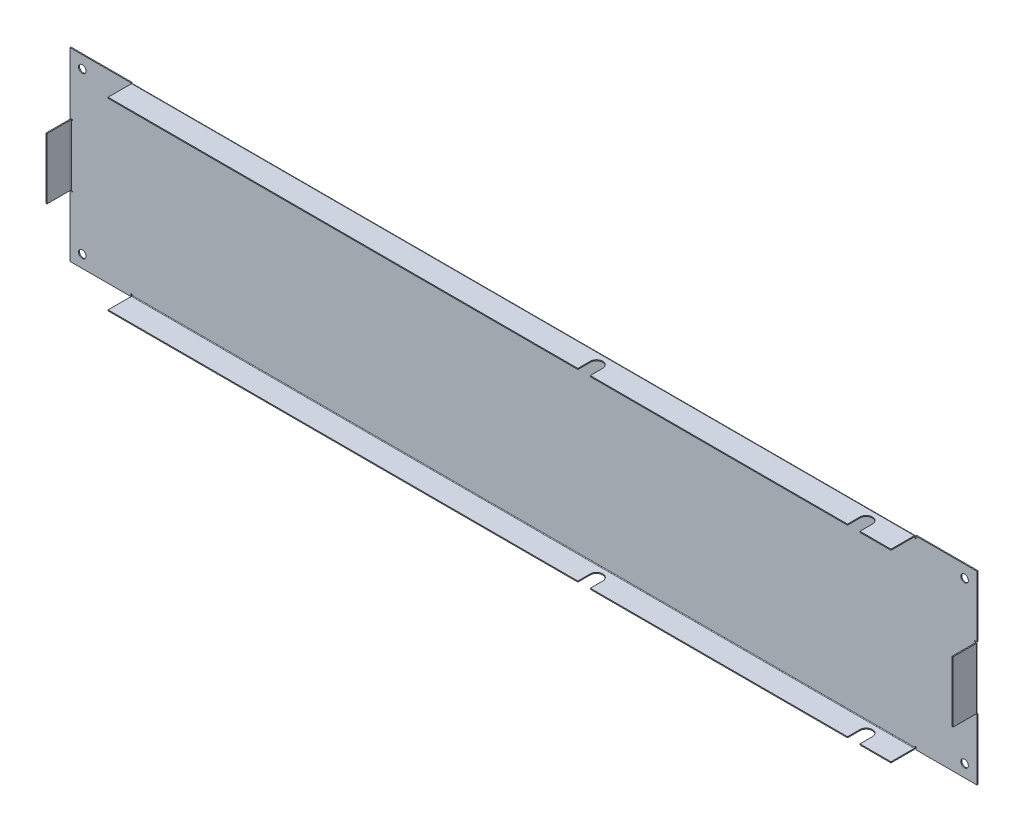
SolidWorks part; units mm, degrees
note: The reader was unsure of these and kept them because the rebuilt part matched: flange length of "边线-法兰1", "边线-法兰2", "边线-法兰3".
ref_plane "前视基准面" through (0, 0, 0) normal (0, 0, 1) x (1, 0, 0)
ref_plane "上视基准面" through (0, 0, 0) normal (0, 1, 0) x (1, 0, 0)
ref_plane "右视基准面" through (0, 0, 0) normal (1, 0, 0) x (0, 0, -1)
sketch "草图1" plane through (0, 0, 0) normal (0, 0, 1) x (1, 0, 0)
  line L1 (-365, 74.5) -> (365, 74.5)
  line L2 (-365, 74.5) -> (-365, -74.5)
  line L3 (-365, -74.5) -> (365, -74.5)
  line L4 (365, 74.5) -> (365, -74.5)
  line L5 (-365, 74.5) -> (365, -74.5) construction
  line L6 (-365, -74.5) -> (365, 74.5) construction
  circle A0 centre (-355, 64.5) radius 3
  circle A1 centre (-355, -64.5) radius 3
  circle A2 centre (355, 64.5) radius 3
  circle A3 centre (355, -64.5) radius 3
  point P0 (0, 0)
  dimension "D11" = 6
  dimension "D1" = 730
  dimension "D2" = 149
  dimension "D3" = 10
  dimension "D4" = 10
  dimension "D5" = 10
  dimension "D6" = 10
  dimension "D7" = 10
  dimension "D8" = 10
  dimension "D9" = 10
  dimension "D10" = 10
base flange "基体-法兰1" sketch "草图1" thickness 0.8 reverse thickness direction no parameters "D1"=0.5
edge flange "边线-法兰1" sketch "草图8" flange angle 90 flange length 20 flange position material inside bend radius 0.5 thickness 0.8 relief rectangular parameters "D6"=10
sketch "草图8" plane through (-365, 0, 0) normal (-1, 0, 0) x (0, -1, 0)
  line L2 (-24.5, 0) -> (-24.5, 19.2)
  line L3 (-24.5, 19.2) -> (24.5, 19.2)
  line L4 (24.5, 19.2) -> (24.5, 0)
  line L5 (-74.5, 0) -> (74.5, 0) construction
  line L6 (-24.5, 0) -> (24.5, 0)
  line L7 (-74.5, -0.8) -> (-74.5, 0) construction
  line L8 (74.5, -0.8) -> (74.5, 0) construction
  line L9 (-74.5, -0.8) -> (74.5, -0.8) construction
  dimension "D1" = 50
  dimension "D2" = 50
  dimension "D3" = 20
bend "边线折弯1" bend radius 0.5 bend angle 90 parameters "D5"=1
edge flange "边线-法兰2" sketch "草图11" flange angle 90 flange length 20 flange position material inside bend radius 0.5 thickness 0.8 relief rectangular parameters "D6"=10
sketch "草图11" plane through (365, 0, 0) normal (1, 0, 0) x (0, 1, 0)
  line L0 (-74.5, 0) -> (74.5, 0) construction
  line L1 (-24.5, 0) -> (24.5, 0)
  line L2 (-24.5, 0) -> (-24.5, 19.2)
  line L3 (-24.5, 19.2) -> (24.5, 19.2)
  line L4 (24.5, 19.2) -> (24.5, 0)
  line L5 (74.5, -0.8) -> (74.5, 0) construction
  line L6 (-74.5, -0.8) -> (74.5, -0.8) construction
  line L7 (-74.5, -0.8) -> (-74.5, 0) construction
  dimension "D1" = 50
  dimension "D2" = 20
  dimension "D3" = 50
bend "边线折弯2" bend radius 0.5 bend angle 90 parameters "D5"=2
edge flange "边线-法兰3" sketch "草图14" flange angle 90 flange length 20 flange position material inside bend radius 0.5 thickness 0.8 relief rectangular parameters "D6"=10
sketch "草图14" plane through (0, 74.5, 0) normal (0, 1, 0) x (-1, 0, 0)
  line L2 (-315, 0) -> (-315, 19.2)
  line L3 (-315, 19.2) -> (-290, 19.2)
  line L4 (315, 19.2) -> (315, 0)
  line L5 (-365, 0) -> (365, 0) construction
  line L6 (-315, 0) -> (315, 0)
  line L7 (-365, -0.8) -> (-365, 0) construction
  line L8 (365, -0.8) -> (365, 0) construction
  line L9 (-290, 9.2) -> (-290, 19.2)
  line L10 (-280, 9.2) -> (-280, 19.2)
  line L11 (-73, 9.2) -> (-73, 19.2)
  line L12 (-63, 9.2) -> (-63, 19.2)
  line L13 (-63, 19.2) -> (315, 19.2)
  line L14 (-280, 19.2) -> (-73, 19.2)
  line L15 (-365, -0.8) -> (365, -0.8) construction
  arc A0 (-290, 9.2) -> (-280, 9.2) centre (-285, 9.2) ccw
  arc A1 (-73, 9.2) -> (-63, 9.2) centre (-68, 9.2) ccw
  dimension "D3" = 10
  dimension "D4" = 10
  dimension "D1" = 50
  dimension "D2" = 50
  dimension "D5" = 20
  dimension "D6" = 10
  dimension "D7" = 10
  dimension "D8" = 30
  dimension "D9" = 217
bend "边线折弯3" bend radius 0.5 bend angle 90 parameters "D5"=3
mirror "镜向1" about plane through (0, 0, 0) normal (0, 1, 0) of "边线-法兰3"
bend "镜向折弯1" bend radius 0.5 bend angle 90 parameters "D5"=4
sketch "折弯-线1" plane through (0, 0, 0) normal (0, 1, 0) x (1, 0, 0)
sketch "边界框1" plane through (0, 0, 0) normal (0, 1, 0) x (1, 0, 0)
sheet metal parameters "钣金1" thickness 0.8 parameters "D1"=0.5
flat pattern "平板型式1" [suppressed]
sketch "折弯-线2" plane through (0, 0, 0) normal (0, 1, 0) x (1, 0, 0)
sketch "边界框2" [suppressed] plane through (0, 0, 0) normal (0, 1, 0) x (1, 0, 0)
sheet metal parameters "钣金2" thickness 0.8 parameters "D1"=0.5
flat pattern "平板型式1" [suppressed]
sketch "折弯-线2" plane through (0, 0, 0) normal (0, 1, 0) x (1, 0, 0)
sketch "边界框2" [suppressed] plane through (0, 0, 0) normal (0, 1, 0) x (1, 0, 0)
bend of the flat pattern "展开-<边线折弯1>1"
sheet metal parameters "钣金3" thickness 0.8 parameters "D1"=0.5
flat pattern "平板型式1" [suppressed]
sketch "折弯-线2" plane through (0, 0, 0) normal (0, 1, 0) x (1, 0, 0)
sketch "边界框2" [suppressed] plane through (0, 0, 0) normal (0, 1, 0) x (1, 0, 0)
bend of the flat pattern "展开-<边线折弯1>1"
bend of the flat pattern "展开-<边线折弯2>1"
sheet metal parameters "钣金4" thickness 0.8 parameters "D1"=0.5
flat pattern "平板型式1" [suppressed]
sketch "折弯-线2" plane through (0, 0, 0) normal (0, 1, 0) x (1, 0, 0)
sketch "边界框2" [suppressed] plane through (0, 0, 0) normal (0, 1, 0) x (1, 0, 0)
bend of the flat pattern "展开-<边线折弯1>1"
bend of the flat pattern "展开-<边线折弯2>1"
bend of the flat pattern "展开-<边线折弯3>1"
sheet metal parameters "钣金5" thickness 0.8 parameters "D1"=0.5
flat pattern "平板型式1" [suppressed]
sketch "折弯-线2" plane through (0, 0, 0) normal (0, 1, 0) x (1, 0, 0)
sketch "边界框2" [suppressed] plane through (0, 0, 0) normal (0, 1, 0) x (1, 0, 0)
bend of the flat pattern "展开-<边线折弯1>1"
bend of the flat pattern "展开-<边线折弯2>1"
bend of the flat pattern "展开-<边线折弯3>1"
bend of the flat pattern "展开-<镜向折弯1>1"
